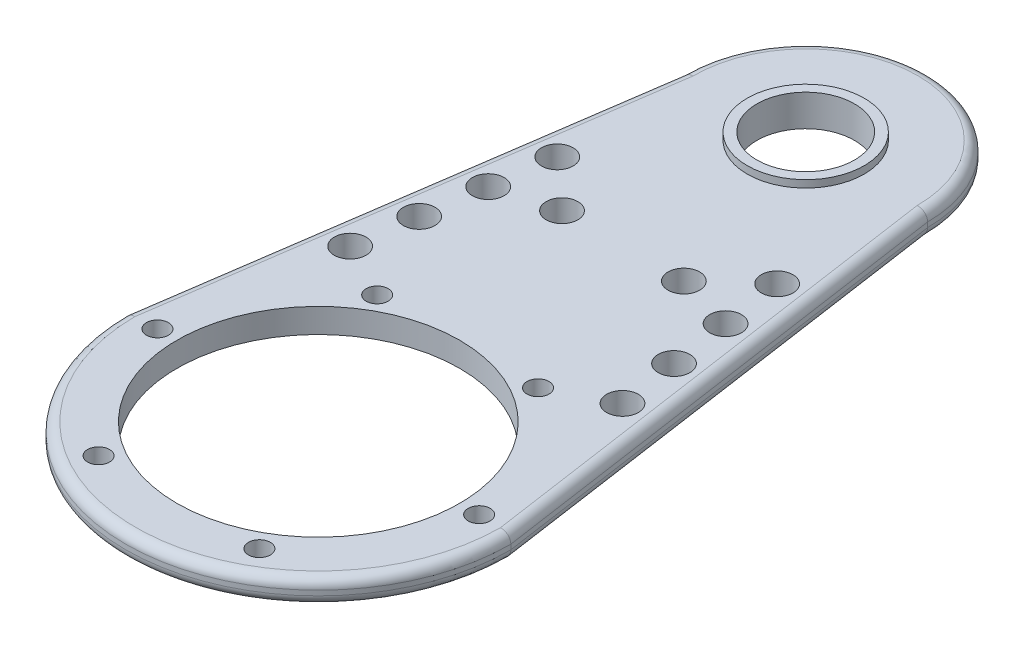
SolidWorks part; units mm, degrees
ref_plane "Front Plane" through (0, 0, 0) normal (0, 0, 1) x (1, 0, 0)
ref_plane "Top Plane" through (0, 0, 0) normal (0, 1, 0) x (1, 0, 0)
ref_plane "Right Plane" through (0, 0, 0) normal (1, 0, 0) x (0, 0, -1)
sketch "Sketch1" plane through (0, 0, 0) normal (0, 1, 0) x (1, 0, 0)
  line L0 (0, 0) -> (33, 0) construction
  line L1 (0, 0) -> (0, 100) construction
  line L6 (39.5, 0) -> (25, 100)
  line L7 (-39.5, 0) -> (-25, 100)
  arc A0 (-39.5, 0) -> (39.5, 0) centre (0, 0) ccw
  circle A1 centre (0, 0) radius 29
  circle A3 centre (33, 0) radius 2.25
  circle A4 centre (16.5, -28.5788) radius 2.25
  circle A5 centre (-16.5, -28.5788) radius 2.25
  circle A6 centre (-33, 0) radius 2.25
  circle A7 centre (-16.5, 28.5788) radius 2.25
  circle A8 centre (16.5, 28.5788) radius 2.25
  circle A10 centre (0, 100) radius 10
  arc A11 (25, 100) -> (-25, 100) centre (0, 100) ccw
  point P19 (0, 0)
  dimension "D1" = 79
  dimension "D2" = 58
  dimension "D4" = 4.5
  dimension "D7" = 20
  dimension "D8" = 15
  dimension "D3" = 33
  dimension "D6" = 100
  dimension "D5" = 6
extrude "Boss-Extrude1" add sketch "Sketch1" along normal blind 5
ref_axis "Axis1" through (0, 5, 0) along (0, -1, 0)
ref_axis "Axis2" through (16.5, 5, -28.5788) along (0, -1, 0)
sketch "Sketch3" plane through (0, 5, 0) normal (0, 1, 0) x (1, 0, 0)
  line L0 (0, 0) -> (0, 100) construction
sketch "Sketch4" plane through (0, 5, 0) normal (0, 1, 0) x (1, 0, 0)
  circle A0 centre (0, 100) radius 10
  circle A1 centre (0, 100) radius 12
  dimension "D1" = 2
  dimension "D2" = 20
extrude "Boss-Extrude2" add sketch "Sketch4" along normal blind 1.5
sketch "Sketch5" plane through (0, 5, 0) normal (0, 1, 0) x (1, 0, 0)
  line L0 (0, 0) -> (0, 62.5) construction
  line L1 (0, 0) -> (0, 100) construction
  line L2 (0, 62.5) -> (12.5, 62.5) construction
  line L3 (0, 62.5) -> (-12.5, 62.5) construction
  line L4 (12.5, 62.5) -> (12.5, 65.75) construction
  circle A0 centre (12.5, 62.5) radius 3.25
  circle A1 centre (-12.5, 62.5) radius 3.25
  dimension "D3" = 6.5
  dimension "D1" = 62.5
  dimension "D2" = 12.5
extrude "Cut-Extrude1" cut sketch "Sketch5" against normal blind 10
sketch "Sketch12" plane through (0, 5, 0) normal (0, 1, 0) x (1, 0, 0)
  line L0 (31.6761, 53.9577) -> (28.0887, 78.6989)
  line L1 (39.5, 0) -> (25, 100) construction
  line L2 (31.6761, 53.9577) -> (35.2636, 29.2164)
  line L3 (35.2636, 29.2164) -> (22.3982, 27.3509)
  line L4 (22.3982, 27.3509) -> (15.2232, 76.8334)
  line L5 (15.2232, 76.8334) -> (28.0887, 78.6989)
  line L6 (22.5528, 71.5809) -> (21.6559, 77.7662) construction
  line L7 (31.6761, 53.9577) -> (18.8107, 52.0922) construction
  line L8 (25.2434, 53.0249) -> (24.3465, 59.2102) construction
  circle A0 centre (22.5528, 71.5809) radius 3.25
  circle A1 centre (24.3465, 59.2102) radius 3.25
  circle A2 centre (27.934, 34.469) radius 3.25
  circle A3 centre (26.1403, 46.8396) radius 3.25
  dimension "D3" = 6.5
  dimension "D1" = 25
  dimension "D2" = 13
  dimension "D4" = 6.25
extrude "Cut-Extrude5" cut sketch "Sketch12" against normal up to surface (5 mm away) contours A2 | A3 | A1 | A0 region at (22.5528, 5, -71.5809) region at (24.3465, 5, -59.2102) region at (27.934, 5, -34.469) region at (26.1403, 5, -46.8396) up to face at (12.5, 0, -59.25)
mirror "Mirror1" about plane through (0, 0, 0) normal (1, 0, 0) of "Cut-Extrude5"
fillet "Fillet1" radius 2 8 edges at (0, 0, 39.5) (-32.25, 0, -50) (0, 0, -125) (32.25, 0, -50) (0, 5, -125) (-32.25, 5, -50) (0, 5, 39.5) (32.25, 5, -50)
sketch "Sketch6" plane through (0, 5, 0) normal (0, 1, 0) x (1, 0, 0)
  line L0 (0, 0) -> (6.6855, 37.9151) construction
  line L1 (0, 0) -> (-6.6855, 37.9151) construction
  line L2 (0, 0) -> (0, 100) construction
  line L3 (-6.6855, 37.9151) -> (-5.0358, 28.5594)
  line L4 (5.0358, 28.5594) -> (6.6855, 37.9151)
  arc A0 (6.6855, 37.9151) -> (-6.6855, 37.9151) centre (0, 0) ccw
  circle A1 centre (0, 0) radius 29 construction
  arc A2 (5.0358, 28.5594) -> (-5.0358, 28.5594) centre (0, 0) ccw
  dimension "D1" = 77
  dimension "D2" = 10
  dimension "D3" = 10
